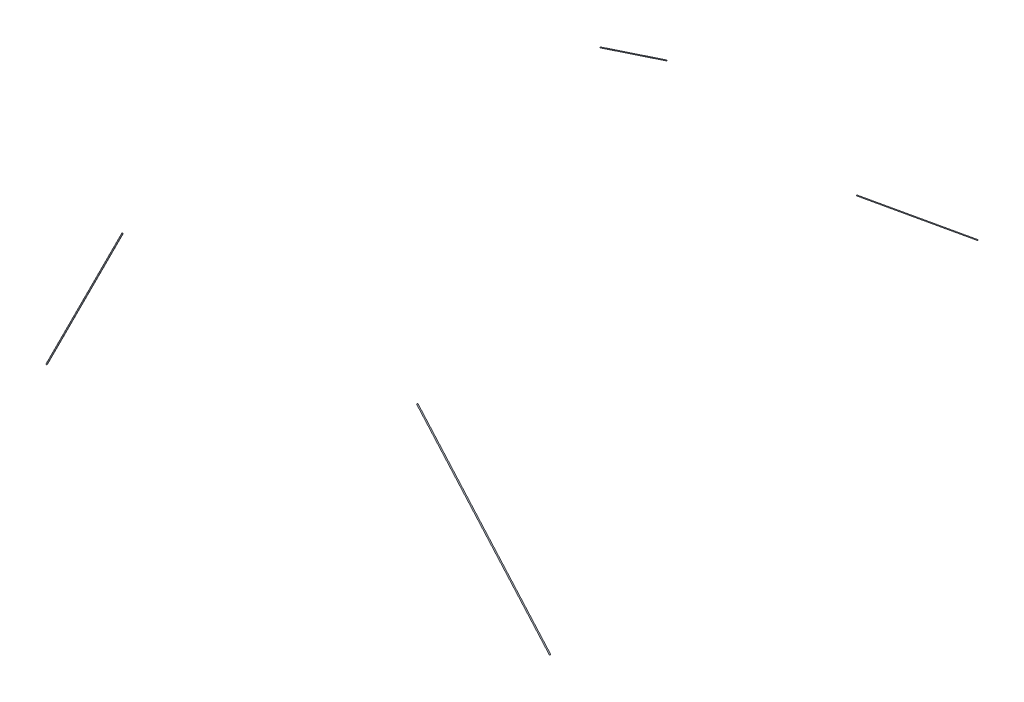
SolidWorks part; units mm, degrees
ref_plane "Front Plane" through (0, 0, 0) normal (0, 0, 1) x (1, 0, 0)
ref_plane "Top Plane" through (0, 0, 0) normal (0, 1, 0) x (1, 0, 0)
ref_plane "Right Plane" through (0, 0, 0) normal (1, 0, 0) x (0, 0, -1)
sketch3d "3DSketch1"
  line L2 (346.493, 181.0469, -995.1413) -> (285.4746, 341.1379, -786.4613) construction
  line L3 (346.493, 181.0469, -995.1413) -> (285.4746, 341.1379, -786.4613)
sweep "Sweep1" add path "3DSketch1" circular profile diameter 1.5875 parameters "D3"=1.5875
sketch3d "3DSketch2"
  line L1 (560.6789, 71.5127, 171.8001) -> (328.3821, 471.4714, 235.4698) construction
  line L2 (560.6789, 71.5127, 171.8001) -> (328.3821, 471.4714, 235.4698)
sweep "Sweep2" add path "3DSketch2" circular profile diameter 2.3813 parameters "D3"=2.3813
ref_plane "Plane1" through (0, 0, 0) normal (1, 0, 0) x (0, 0, -1)
mirror "Mirror1" about plane through (0, 0, 0) normal (1, 0, 0) of bodies 101 102
